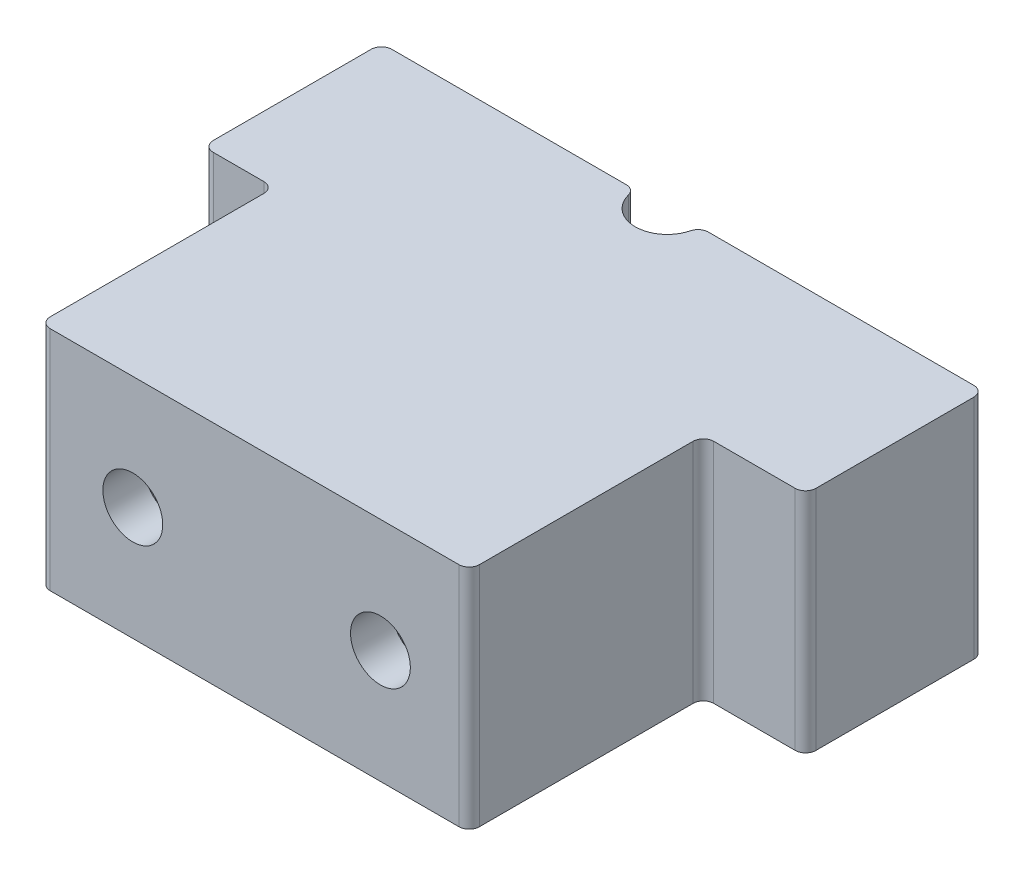
SolidWorks part; units mm, degrees
note: The reader was unsure of these and kept them because the rebuilt part matched: shared geometry of "Sketch1<4>".
ref_plane "Front Plane" through (0, 0, 0) normal (0, 0, 1) x (1, 0, 0)
ref_plane "Top Plane" through (0, 0, 0) normal (0, 1, 0) x (1, 0, 0)
ref_plane "Right Plane" through (0, 0, 0) normal (1, 0, 0) x (0, 0, -1)
sketch "Sketch1" plane through (0, 0, 0) normal (0, 1, 0) x (1, 0, 0)
  line L0 (-1.55, 10) -> (1.55, 10) construction
  line L1 (-10.4, -10) -> (10.4, -10)
  line L2 (-10.4, -10) -> (-10.4, 10)
  line L3 (-10.4, 10) -> (-1.55, 10)
  line L4 (10.4, -10) -> (10.4, 10)
  line L5 (-10.4, -10) -> (10.4, 10) construction
  line L6 (-10.4, 10) -> (10.4, -10) construction
  line L7 (1.55, 10) -> (10.4, 10)
  line L8 (0, 10) -> (0, -10) construction
  line L9 (-10.4, 10) -> (-13.85, 10)
  line L10 (-13.85, 10) -> (-13.85, 1.35)
  line L11 (-13.85, 1.35) -> (-10.4, 1.35)
  line L12 (10.4, 10) -> (15.35, 10)
  line L13 (15.35, 10) -> (15.35, 1.35)
  line L14 (15.35, 1.35) -> (10.4, 1.35)
  arc A0 (-1.55, 10) -> (1.55, 10) centre (0, 10) ccw
  arc A1 (1.55, 10) -> (-1.55, 10) centre (0, 10) ccw construction
  point P0 (0, 0)
  dimension "D1" = 3.1
  dimension "D2" = 20
  dimension "D3" = 20.8
  dimension "D4" = 8.65
  dimension "D5" = 3.45
  dimension "D6" = 4.95
extrude "Boss-Extrude1" add sketch "Sketch1" along normal blind 11 contours A0 L3 L2 L1 L4 L7
sketch "Sketch2" plane through (0, 0, 10) normal (0, 0, 1) x (1, 0, 0)
  line L0 (10.4, 5.5) -> (-10.4, 5.5) construction
  line L1 (10.4, 11) -> (10.4, 0) construction
  line L2 (-10.4, 11) -> (-10.4, 0) construction
  circle A0 centre (-5.9, 5.5) radius 1.45
  circle A1 centre (6.1, 5.5) radius 1.45
  dimension "D3" = 2.9
  dimension "D4" = 2.9
  dimension "D1" = 12
  dimension "D2" = 4.5
extrude "Cut-Extrude1" cut sketch "Sketch2" against normal blind 8
sketch "Sketch3" plane through (0, 0, -10) normal (0, 0, -1) x (-1, 0, 0)
  line L0 (-10.4, 5.5) -> (10.4, 5.5) construction
  line L1 (-10.4, 11) -> (-10.4, 0) construction
  line L2 (10.4, 11) -> (10.4, 0) construction
  line L5 (0, 0) -> (0, 11) construction
  line L6 (-1.55, 0) -> (1.55, 0) construction
  line L7 (1.55, 11) -> (-1.55, 11) construction
  circle A0 centre (-8.1, 5.5) radius 1.5
  circle A1 centre (8.1, 5.5) radius 1.5
  dimension "D1" = 3
  dimension "D2" = 3
  dimension "D3" = 8.1
  dimension "D4" = 8.1
extrude "Cut-Extrude2" cut sketch "Sketch3" against normal blind 10
ref_plane "Plane1" through (0, 0, -8) normal (0, 0, -1) x (-1, 0, 0)
ref_plane "Plane2" through (0, 0, 8) normal (0, 0, 1) x (1, 0, 0)
sketch "Sketch6" plane through (0, 0, 10) normal (0, 0, 1) x (1, 0, 0)
  line L0 (-10.4, 11) -> (-10.4, 0) construction
  line L1 (-5.9, 8.56) -> (-8.55, 7.03)
  line L2 (-8.55, 7.03) -> (-8.55, 3.97)
  line L3 (-7.225, 3.205) -> (-5.9, 2.44) construction
  line L4 (-4.575, 3.205) -> (-3.25, 3.97) construction
  line L5 (-3.25, 3.97) -> (-3.25, 7.03)
  line L6 (-3.25, 7.03) -> (-5.9, 8.56)
  line L7 (-8.55, 3.97) -> (-8.55, 0)
  line L8 (6.1, 8.56) -> (3.45, 7.03)
  line L9 (3.45, 7.03) -> (3.45, 3.97)
  line L10 (4.775, 3.205) -> (6.1, 2.44) construction
  line L11 (7.425, 3.205) -> (8.75, 3.97) construction
  line L12 (8.75, 3.97) -> (8.75, 7.03)
  line L13 (8.75, 7.03) -> (6.1, 8.56)
  line L15 (-8.55, 0) -> (-3.25, 0)
  line L16 (-3.25, 0) -> (-3.25, 3.97)
  line L17 (3.45, 3.97) -> (3.45, 0)
  line L18 (3.45, 0) -> (8.75, 0)
  line L19 (8.75, 0) -> (8.75, 3.97)
  line L20 (10.4, 11) -> (10.4, 0) construction
  line L21 (-8.55, 3.97) -> (-7.225, 3.205) construction
  line L22 (-5.9, 2.44) -> (-4.575, 3.205) construction
  line L23 (3.45, 3.97) -> (4.775, 3.205) construction
  line L24 (6.1, 2.44) -> (7.425, 3.205) construction
  line L25 (-10.4, 0) -> (10.4, 0) construction
  arc A0 (-3.25, 5.5) -> (-8.55, 5.5) centre (-5.9, 5.5) ccw construction
  arc A1 (8.75, 5.5) -> (3.45, 5.5) centre (6.1, 5.5) ccw construction
  arc A2 (-8.55, 5.5) -> (-7.225, 3.205) centre (-5.9, 5.5) ccw construction
  arc A3 (-7.225, 3.205) -> (-4.575, 3.205) centre (-5.9, 5.5) ccw construction
  arc A4 (-4.575, 3.205) -> (-3.25, 5.5) centre (-5.9, 5.5) ccw construction
  arc A5 (3.45, 5.5) -> (4.775, 3.205) centre (6.1, 5.5) ccw construction
  arc A6 (4.775, 3.205) -> (7.425, 3.205) centre (6.1, 5.5) ccw construction
  arc A7 (7.425, 3.205) -> (8.75, 5.5) centre (6.1, 5.5) ccw construction
  dimension "D2" = 5.3
extrude "Cut-Extrude4" cut sketch "Sketch6" against normal blind 2.4 from surface at -2 starting at plane "Plane2"
extrude "Boss-Extrude2" add sketch "Sketch1<4>" along normal through all contours L14 L13 L12 L4 | L10 L11 L2 L9
sketch "Sketch1<4>" plane through (0, 0, 0) normal (0, 1, 0) x (1, 0, 0) same geometry as "Sketch1"
sketch "Sketch5" plane through (0, 0, -10) normal (0, 0, -1) x (-1, 0, 0)
  line L0 (-1.55, 11) -> (-1.55, 0) construction
  line L1 (-8.1, 2.4689) -> (-6.7875, 3.2267) construction
  line L2 (-5.475, 3.9845) -> (-5.475, 7.0155)
  line L3 (-5.475, 7.0155) -> (-8.1, 8.5311)
  line L4 (-8.1, 8.5311) -> (-10.725, 7.0155)
  line L5 (-10.725, 7.0155) -> (-10.725, 3.9845)
  line L6 (-10.725, 3.9845) -> (-9.4125, 3.2267) construction
  line L7 (9.4125, 3.2267) -> (10.725, 3.9845) construction
  line L8 (10.725, 3.9845) -> (10.725, 7.0155)
  line L9 (10.725, 7.0155) -> (8.1, 8.5311)
  line L10 (8.1, 8.5311) -> (5.475, 7.0155)
  line L11 (5.475, 7.0155) -> (5.475, 3.9845)
  line L12 (6.7875, 3.2267) -> (8.1, 2.4689) construction
  line L13 (-1.55, 0) -> (-15.35, 0) construction
  line L16 (-10.725, 3.9845) -> (-10.725, 0)
  line L17 (-1.55, 11) -> (-1.55, 0) construction
  line L18 (-10.725, 0) -> (-5.475, 0)
  line L19 (-5.475, 0) -> (-5.475, 3.9845)
  line L20 (5.475, 3.9845) -> (5.475, 0)
  line L21 (1.55, 11) -> (1.55, 0) construction
  line L22 (5.475, 0) -> (10.725, 0)
  line L23 (10.725, 0) -> (10.725, 3.9845)
  line L24 (5.475, 3.9845) -> (6.7875, 3.2267) construction
  line L25 (8.1, 2.4689) -> (9.4125, 3.2267) construction
  line L26 (-6.7875, 3.2267) -> (-5.475, 3.9845) construction
  line L27 (-9.4125, 3.2267) -> (-8.1, 2.4689) construction
  line L28 (13.85, 0) -> (1.55, 0) construction
  arc A0 (-5.475, 5.5) -> (-10.725, 5.5) centre (-8.1, 5.5) ccw construction
  arc A1 (10.725, 5.5) -> (5.475, 5.5) centre (8.1, 5.5) ccw construction
  arc A2 (5.475, 5.5) -> (6.7875, 3.2267) centre (8.1, 5.5) ccw construction
  arc A3 (6.7875, 3.2267) -> (9.4125, 3.2267) centre (8.1, 5.5) ccw construction
  arc A4 (9.4125, 3.2267) -> (10.725, 5.5) centre (8.1, 5.5) ccw construction
  arc A5 (-6.7875, 3.2267) -> (-5.475, 5.5) centre (-8.1, 5.5) ccw construction
  arc A6 (-9.4125, 3.2267) -> (-6.7875, 3.2267) centre (-8.1, 5.5) ccw construction
  arc A7 (-10.725, 5.5) -> (-9.4125, 3.2267) centre (-8.1, 5.5) ccw construction
  dimension "D1" = 5.25
  dimension "D2" = 3.925
  dimension "D3" = 5.25
extrude "Cut-Extrude3" cut sketch "Sketch5" against normal blind 2.4 from surface at -2
fillet "Fillet2" radius 0.5 10 edges at (-10.4, 5.5, 10) (10.4, 5.5, 10) (-1.55, 5.5, -10) (1.55, 5.5, -10) (-13.85, 5.5, -10) (-13.85, 5.5, -1.35) (-10.4, 5.5, -1.35) (15.35, 5.5, -1.35) (15.35, 5.5, -10) (10.4, 5.5, -1.35)
equation "\"D4@Sketch2\"=\"D3@Sketch2\""
equation "\"D2@Sketch3\"=\"D1@Sketch3\""
equation "\"D3@Sketch5\"=\"D1@Sketch5\""
equation "\"D2@Sketch6\"=\"D1@Sketch6\""
